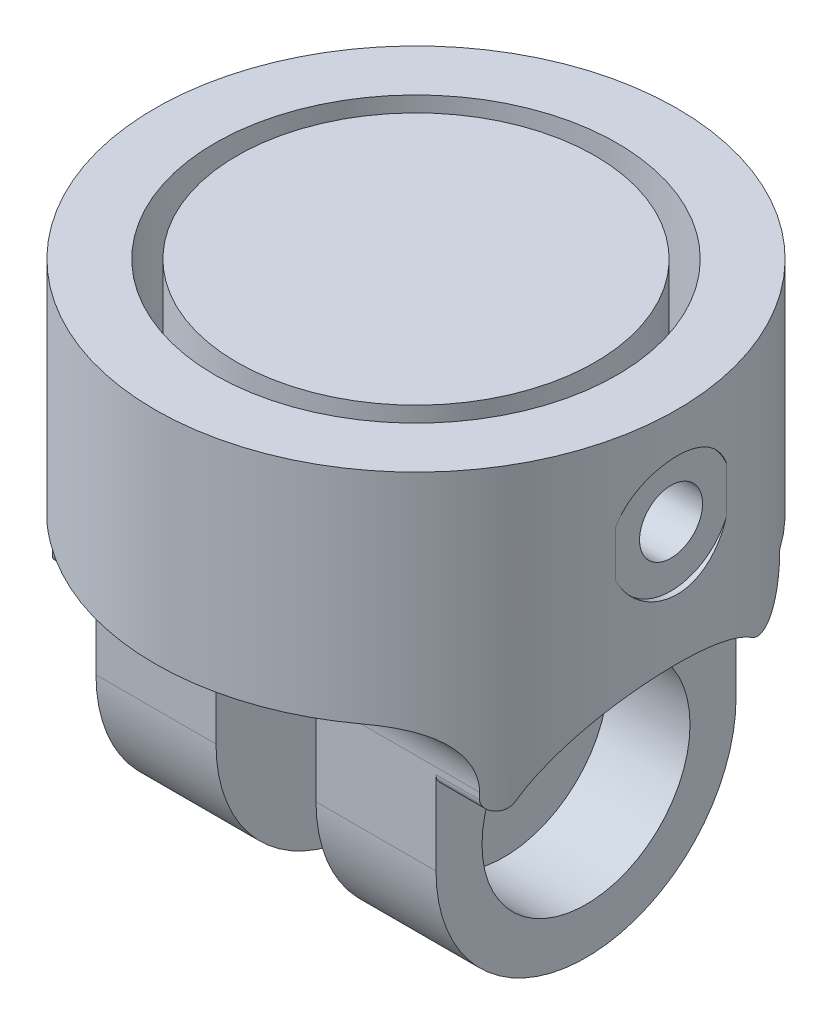
SolidWorks part; units mm, degrees
material "PLA Black"
ref_plane "Front" through (0, 0, 0) normal (0, 0, 1) x (1, 0, 0)
ref_plane "Top" through (0, 0, 0) normal (0, 1, 0) x (1, 0, 0)
ref_plane "Right" through (0, 0, 0) normal (1, 0, 0) x (0, 0, -1)
sketch "Sketch1" plane through (0, 0, 0) normal (0, 1, 0) x (1, 0, 0)
  line L0 (0, 8.95) -> (0, 10.05) construction
  circle A0 centre (0, 0) radius 10.05
  circle A1 centre (0, 0) radius 13.05
  circle A2 centre (0, 0) radius 9.5 construction
  circle A4 centre (0, 0) radius 8.95
  point P11 (0, 9.5)
  dimension "D1" = 1.1
  dimension "D2" = 3
  dimension "D3" = 19
extrude "Boss-Extrude1" add sketch "Sketch1" along normal blind 10 contours A1 A0 | A4 region at (-12.6809, 0, 0) region at (0, 0, 0)
sketch "Sketch3" plane through (0, 0, 0) normal (0, -1, 0) x (1, 0, 0)
  circle A2 centre (0, 0) radius 13.05 construction
  circle A3 centre (0, 0) radius 13.05
extrude "Boss-Extrude2" add sketch "Sketch3" along normal blind 1
sketch "Sketch4" plane through (0, -1, 0) normal (0, -1, 0) x (1, 0, 0)
  line L0 (0, 17.8908) -> (0, -17.0763) construction
  line L1 (2.5, 7.5) -> (8.5, 7.5)
  line L2 (2.5, 7.5) -> (2.5, -7.5)
  line L3 (2.5, -7.5) -> (8.5, -7.5)
  line L4 (8.5, 7.5) -> (8.5, -7.5)
  line L5 (-8.5, 7.5) -> (-8.5, -7.5)
  line L6 (-2.5, -7.5) -> (-8.5, -7.5)
  line L7 (-2.5, 7.5) -> (-2.5, -7.5)
  line L8 (-2.5, 7.5) -> (-8.5, 7.5)
  line L9 (16.8049, 0) -> (-19.8998, 0) construction
  dimension "D1" = 6
  dimension "D2" = 5
  dimension "D3" = 15
extrude "Boss-Extrude3" add sketch "Sketch4" along normal blind 15
sketch "Sketch5" plane through (8.5, 0, 0) normal (1, 0, 0) x (0, 0, -1)
  line L0 (-7.5, -16) -> (-7.5, -1) construction
  line L1 (7.5, -16) -> (7.5, -1) construction
  line L2 (7.5, -8.5) -> (7.5, -17.1619)
  line L3 (7.5, -17.1619) -> (-7.5, -17.1619)
  line L4 (-7.5, -17.1619) -> (-7.5, -8.5)
  arc A0 (-7.5, -8.5) -> (7.5, -8.5) centre (0, -8.5) ccw
  circle A1 centre (0, -8.5) radius 1.55
  dimension "D1" = 3.1
extrude "Cut-Extrude1" cut sketch "Sketch5" against normal through all both and the other way through all
sketch "Sketch6" plane through (8.5, 0, 0) normal (1, 0, 0) x (0, 0, -1)
  circle A0 centre (0, -8.5) radius 5.2
  dimension "D1" = 10.4
extrude "Cut-Extrude2" cut sketch "Sketch6" against normal blind 4.1
mirror "Mirror1" about plane through (0, 0, 0) normal (1, 0, 0) of "Cut-Extrude2"
ref_plane "Plane9" through (1.335, 0, 0) normal (1, 0, 0) x (0, 0, -1)
sketch "Sketch7" plane through (1.335, 0, 0) normal (1, 0, 0) x (0, 0, -1)
  line L0 (3.555, -8.5) -> (3.555, -1) construction
  line L1 (7.5, -1) -> (-7.5, -1) construction
  line L2 (3.4474, -7.632) -> (1.7775, -1) construction
  line L3 (3.1303, -6.8149) -> (0, -1) construction
  line L4 (1.7775, -0.6757) -> (1.7775, -1.4422) construction
  line L5 (2.6911, -6.1771) -> (-1.7775, -1) construction
  line L6 (2.2506, -5.7481) -> (-3.555, -1) construction
  line L8 (0, -1.6788) -> (0, 0) construction
  line L9 (-8.4824, -8.5) -> (8.712, -8.5) construction
  line L10 (1.8766, -5.4807) -> (-5.3325, -1) construction
  line L11 (-3.555, -0.3587) -> (-3.555, -1.6788) construction
  circle A0 centre (0, -8.5) radius 3.555 construction
  dimension "D1" = 7.11
  dimension "D2" = 31.862
  dimension "D3" = 7.5
ref_plane "Plane1" through (1.335, -1, -3.555) normal (0, 1, 0) x (1, 0, 0)
ref_plane "Plane2" through (1.335, -1, -1.7775) normal (0, 0.9697, 0.2442) x (1, 0, 0)
ref_plane "Plane3" through (1.335, -1, 0) normal (0, 0.8805, 0.474) x (1, 0, 0)
ref_plane "Plane5" through (1.335, -1, 1.7775) normal (0, 0.757, 0.6534) x (1, 0, 0)
ref_plane "Plane6" through (1.335, -1, 3.555) normal (0, 0.6331, 0.7741) x (1, 0, 0)
ref_plane "Plane7" through (1.335, -1, 5.3325) normal (0, 0.5279, 0.8493) x (1, 0, 0)
sketch "Sketch8" plane through (1.335, -1, -3.555) normal (0, 1, 0) x (1, 0, 0)
  circle A0 centre (0, 0) radius 0.4895
  dimension "D1" = 0.979
extrude "Cut-Extrude5" cut sketch "Sketch8" along normal blind 5.5 and the other way through all
sketch "Sketch9" plane through (1.335, -1, -1.7775) normal (0, 0.9697, 0.2442) x (1, 0, 0)
  circle A0 centre (0, 0) radius 0.4895
  dimension "D1" = 0.979
extrude "Cut-Extrude3" cut sketch "Sketch9" along normal blind 5.5
sketch "Sketch10" plane through (1.335, -1, 0) normal (0, 0.8805, 0.474) x (1, 0, 0)
  circle A0 centre (0, 0) radius 0.4895
  dimension "D1" = 0.979
sketch "Sketch11" plane through (1.335, -1, 1.7775) normal (0, 0.757, 0.6534) x (1, 0, 0)
  circle A0 centre (0, 0) radius 0.4895
  dimension "D1" = 0.979
sketch "Sketch12" plane through (1.335, -1, 3.555) normal (0, 0.6331, 0.7741) x (1, 0, 0)
  circle A0 centre (0, 0) radius 0.4895
  dimension "D1" = 0.979
sketch "Sketch14" plane through (1.335, -1, 5.3325) normal (0, 0.5279, 0.8493) x (1, 0, 0)
  circle A0 centre (0, 0) radius 0.4895
  dimension "D1" = 0.979
extrude "Cut-Extrude6" cut sketch "Sketch10" along normal blind 5.5 and the other way through all
extrude "Cut-Extrude7" cut sketch "Sketch11" along normal blind 5.5 and the other way through all contours A0
extrude "Cut-Extrude8" cut sketch "Sketch12" along normal blind 5.5 and the other way through all contours A0
extrude "Cut-Extrude9" cut sketch "Sketch14" along normal blind 5.5 and the other way through all contours A0
ref_plane "Plane8" through (13.05, 0, 0) normal (1, 0, 0) x (0, 0, -1)
hole_wizard "Tap Drill for M3 Helicoil1" positions "Sketch17" profile "Sketch18" hole size "M3x0.5" standard "DIN"
sketch "Sketch17" plane through (13.05, 0, 0) normal (1, 0, 0) x (0, 0, -1)
  line L0 (-22.2973, 5) -> (18.0703, 5) construction
  line L4 (0, 12.2732) -> (0, -5.3405) construction
  line L6 (-7.5, -8.5) -> (-7.5, -1) construction
  line L7 (7.5, -8.5) -> (7.5, -1) construction
  line L8 (13.05, 10) -> (-13.05, 10) construction
  line L9 (10.05, 0) -> (-10.05, 0) construction
  point P0 (0, 5)
sketch "Sketch18" plane through (13.05, 5, 0) normal (0, 1, 0) x (0, 0, -1)
  line L0 (0, 0) -> (0, 6.9464)
  line L1 (0, 6.9464) -> (1.575, 6)
  line L2 (1.575, 6) -> (1.575, 0)
  line L5 (1.575, 0) -> (0, 0)
  line L10 (0, 6.9464) -> (-1.575, 6) construction
  line L11 (0, -6.35) -> (0, 107.95) construction
  dimension "Hole Dia." = 3.15
  dimension "Hole Depth" = 6
  dimension "Drill Angle" = 118
sketch "Sketch20" plane through (13.05, 0, 0) normal (1, 0, 0) x (0, 0, -1)
  circle A0 centre (0, 5) radius 3
  dimension "D1" = 6
extrude "Cut-Extrude10" cut sketch "Sketch20" against normal blind 0.3
sketch "Sketch21" plane through (8.5, 0, 0) normal (1, 0, 0) x (0, 0, -1)
  line L0 (7.5, -1) -> (-7.5, -1) construction
  line L1 (7.5, -0.1252) -> (7.5, -1.1767)
  line L2 (0.9244, -19.0662) -> (-4.8209, -14.2453) construction
  line L3 (0, 5.2718) -> (0, -9.2894) construction
  line L4 (0, 10) -> (0, -1) construction
  line L5 (-7.5, -0.1252) -> (-7.5, -4.3226)
  line L6 (7.5, -0.1252) -> (-7.5, -0.1252)
  line L7 (-7.5, -8.5) -> (-7.5, -1) construction
  line L8 (7.5, -8.5) -> (7.5, -1) construction
  line L9 (0, -1) -> (9.4693, -4.4465) construction
  line L10 (0, -1) -> (1.6171, -0.0664) construction
  line L11 (4.6128, -2.5863) -> (7.5, -1.1767) construction
  line L12 (10.5662, -7.5756) -> (4.8209, -2.7547) construction
  line L13 (-4.8209, -14.2453) -> (4.8209, -2.7547) construction
  line L14 (10.5662, -7.5756) -> (0.9244, -19.0662) construction
  arc A0 (-6.4204, -4.6233) -> (4.6128, -2.5863) centre (0, -8.5) cw
  arc A1 (-6.4204, -4.6233) -> (-7.5, -4.3226) centre (-6.9183, -4.3226) cw
  arc A2 (7.5, -1.1767) -> (4.6128, -2.5863) centre (5.7123, -1.1767) cw
  circle A3 centre (0, -8.5) radius 1.55 construction
  arc A4 (-4.8209, -14.2453) -> (4.8209, -2.7547) centre (0, -8.5) cw construction
  dimension "D1" = 30
  dimension "D3" = 7.5
  dimension "D2" = 50
  dimension "D4" = 15
extrude "Boss-Extrude4" add sketch "Sketch21" along normal up to surface (2.1795 mm away) up to face at (12.895, 5, 0)
mirror "Mirror2" about plane through (0, 0, 0) normal (1, 0, 0) of "Boss-Extrude4", "Tap Drill for M3 Helicoil1", "Cut-Extrude10"
fillet "Fillet1" radius 3 2 edges at (-6.5898, -1, 7.5) (6.5898, -1, 7.5)
equation "\"knee_angle\"= 0"
equation "\"ankle_angle\" = 90"
equation "\"hip_angle\" = 30"
equation "\"spring_ankle_parallel_arm_diameter\"= 0.89"
equation "\"spring_ankle_parallel_arm_length\"= 13"
equation "\"spring_ankle_parallel_intern_diameter\"= 6.22"
equation "\"spring_ankle_parallel_angle\"= \"ankle_angle\""
equation "\"spring_ankle_parallel_turns\"= 3"
equation "\"spring_ankle_parallel_pitch\"= \"spring_ankle_parallel_arm_diameter\" * 1.01"
equation "\"spring_ankle_parallel_cutting_distance\"= (1-\"spring_ankle_parallel_angle\" / 360) * \"spring_ankle_parallel_pitch\""
equation "\"spring_ankle_serial_arm_diameter\"= 0.89"
equation "\"spring_ankle_serial_arm_length\"= 10"
equation "\"spring_ankle_serial_intern_diameter\"= 6.22"
equation "\"spring_ankle_serial_angle\"= \"90\""
equation "\"spring_ankle_serial_turns\"= 3"
equation "\"spring_ankle_serial_pitch\"= \"spring_ankle_serial_arm_diameter\" * 1.01"
equation "\"spring_ankle_serial_cutting_distance\"= (1-\"spring_ankle_serial_angle\" / 360) * \"spring_ankle_serial_pitch\""
equation "\"spring_knee_parallel_arm_diameter\"= 0.89"
equation "\"spring_knee_parallel_arm_length\"= 15"
equation "\"spring_knee_parallel_intern_diameter\"= 5.46"
equation "\"spring_knee_parallel_angle\"= \"knee_angle\""
equation "\"spring_knee_parallel_turns\"= 3"
equation "\"spring_knee_parallel_pitch\"= \"spring_knee_parallel_arm_diameter\" * 1.01"
equation "\"spring_knee_parallel_cutting_distance\"= (1 - (90 + \"spring_knee_parallel_angle\") / 360) * \"spring_knee_parallel_pitch\""
equation "\"spring_knee_serial_arm_diameter\"= 0.89"
equation "\"spring_knee_serial_arm_length\"= 10"
equation "\"spring_knee_serial_intern_diameter\"= 5.46"
equation "\"spring_knee_serial_angle\"= \"90\""
equation "\"spring_knee_serial_turns\"= 3"
equation "\"spring_knee_serial_pitch\"= \"spring_knee_serial_arm_diameter\" * 1.01"
equation "\"spring_knee_serial_cutting_distance\"= (1-\"spring_knee_serial_angle\" / 360) * \"spring_knee_serial_pitch\""
equation "\"spring_ankle_parallel_nominal_diameter\"= \"spring_ankle_parallel_arm_diameter\" + \"spring_ankle_parallel_intern_diameter\""
equation "\"spring_ankle_serial_nominal_diameter\"= \"spring_ankle_serial_arm_diameter\" + \"spring_ankle_serial_intern_diameter\""
equation "\"spring_knee_parallel_nominal_diameter\"= \"spring_knee_parallel_arm_diameter\" + \"spring_knee_parallel_intern_diameter\""
equation "\"spring_knee_serial_nominal_diameter\"= \"spring_knee_serial_arm_diameter\" + \"spring_knee_serial_intern_diameter\""
equation "\"D1@Sketch7\"=\"spring_ankle_parallel_nominal_diameter\""
equation "\"D1@Sketch8\"=\"spring_ankle_parallel_arm_diameter\"*1.1"
equation "\"D1@Sketch9\"=\"spring_ankle_parallel_arm_diameter\"*1.1"
equation "\"D1@Sketch10\"=\"spring_ankle_parallel_arm_diameter\"*1.1"
equation "\"D1@Sketch11\"=\"spring_ankle_parallel_arm_diameter\"*1.1"
equation "\"D1@Sketch12\"=\"spring_ankle_parallel_arm_diameter\"*1.1"
equation "\"D1@Sketch14\"=\"spring_ankle_parallel_arm_diameter\"*1.1"
equation "\"D1@Cut-Extrude3\"=\"spring_ankle_parallel_arm_length\"-\"axis_structure_distance\""
equation "\"axis_structure_distance\"= 7.5"
equation "\"D1@Cut-Extrude5\"=\"spring_ankle_parallel_arm_length\"-\"axis_structure_distance\""
equation "\"D1@Cut-Extrude6\"=\"spring_ankle_parallel_arm_length\"-\"axis_structure_distance\""
equation "\"D1@Cut-Extrude7\"=\"spring_ankle_parallel_arm_length\"-\"axis_structure_distance\""
equation "\"D1@Cut-Extrude8\"=\"spring_ankle_parallel_arm_length\"-\"axis_structure_distance\""
equation "\"D1@Cut-Extrude9\"=\"spring_ankle_parallel_arm_length\"-\"axis_structure_distance\""
equation "\"D1@Boss-Extrude3\"=\"axis_structure_distance\"*2"
equation "\"ankle_angle_max\" = 120"
equation "\"ankle_angle_min\" = 50"
equation "\"knee_angle_max\" = 120"
equation "\"knee_angle_min\" = 0"
equation "\"hip_angle_max\" = 45"
equation "\"hip_angle_min\" = -45"
equation "\"D1@Sketch21\"=\"ankle_angle_max\"-90"
equation "\"D2@Sketch21\"=\"ankle_angle_min\""
equation "\"D1@Plane9\"=(\"spring_ankle_parallel_arm_diameter\"*\"spring_ankle_parallel_turns\")/2"
